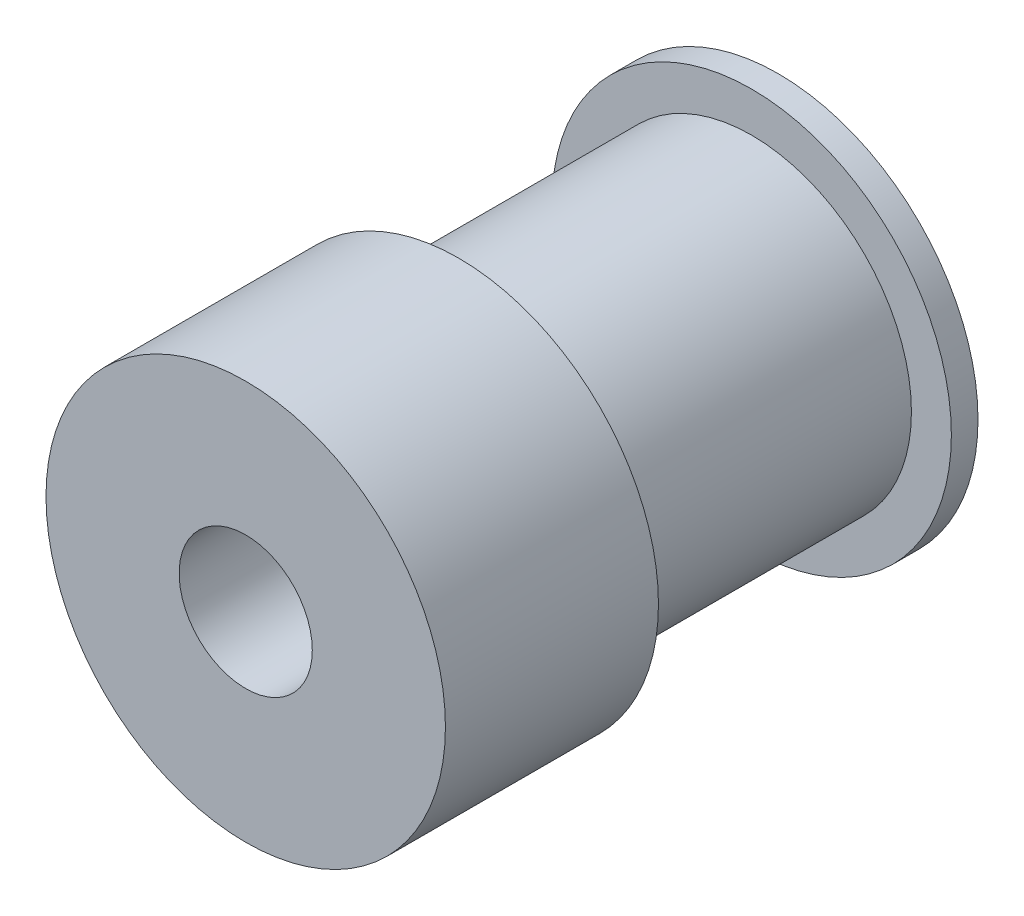
SolidWorks part; units mm, degrees
ref_plane "Alzado" through (0, 0, 0) normal (0, 0, 1) x (1, 0, 0)
ref_plane "Planta" through (0, 0, 0) normal (0, 1, 0) x (1, 0, 0)
ref_plane "Vista lateral" through (0, 0, 0) normal (1, 0, 0) x (0, 0, -1)
sketch "Croquis1" plane through (0, 0, 0) normal (0, 1, 0) x (1, 0, 0)
  line L0 (0, 0) -> (0, 20)
  line L1 (0, 20) -> (7.5, 20)
  line L2 (7.5, 20) -> (7.5, 19)
  line L3 (7.5, 19) -> (6, 19)
  line L4 (6, 19) -> (6, 8)
  line L5 (6, 8) -> (7.5, 8)
  line L6 (7.5, 8) -> (7.5, 0)
  line L7 (7.5, 0) -> (0, 0)
  dimension "D1" = 20
  dimension "D2" = 11
  dimension "D3" = 1
  dimension "D4" = 7.5
  dimension "D5" = 7.5
  dimension "D6" = 6
revolve "Revolución1" add sketch "Croquis1" angle 360 about L0
sketch "Croquis2" plane through (0, 0, 0) normal (0, 0, 1) x (1, 0, 0)
  circle A0 centre (0, 0) radius 2.5
  dimension "D1" = 5
extrude "Cortar-Extruir1" cut sketch "Croquis2" against normal up to surface (20 mm away) up to face at (7.5, 0, -20)
